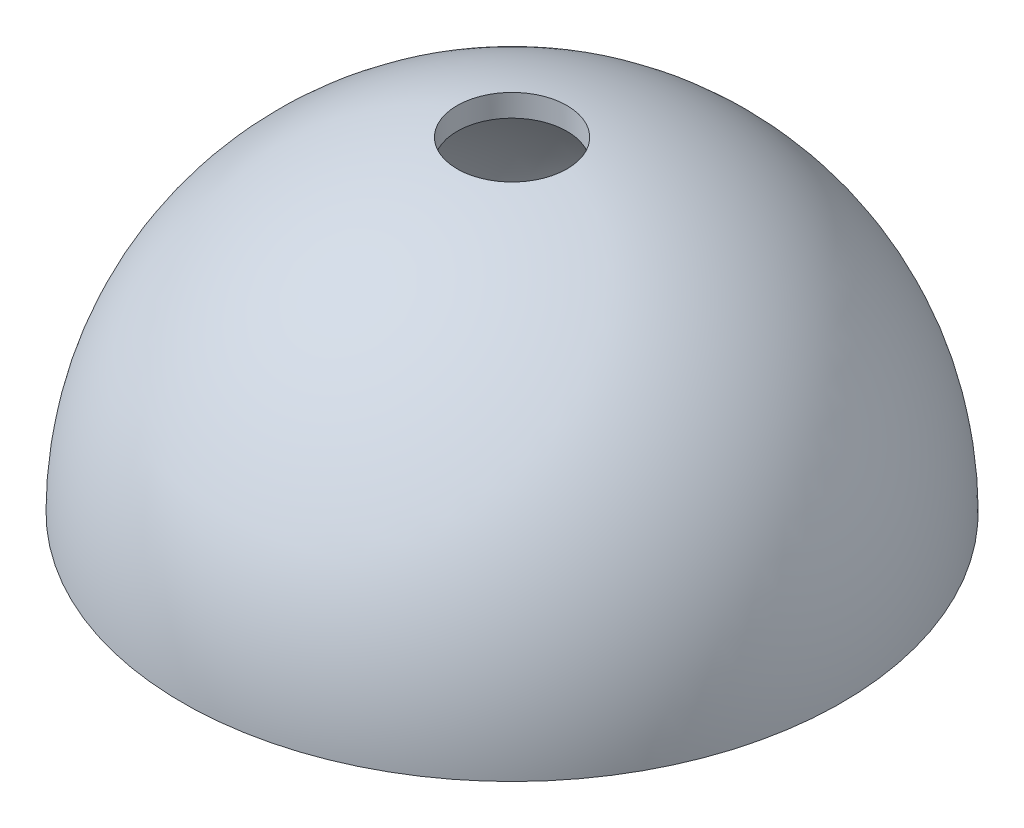
SolidWorks part; units mm, degrees
ref_plane "Front Plane" through (0, 0, 0) normal (0, 0, 1) x (1, 0, 0)
ref_plane "Top Plane" through (0, 0, 0) normal (0, 1, 0) x (1, 0, 0)
ref_plane "Right Plane" through (0, 0, 0) normal (1, 0, 0) x (0, 0, -1)
sketch "Sketch1" plane through (0, 0, 0) normal (0, 0, 1) x (1, 0, 0)
  line L0 (0, 0) -> (0, 150)
  line L1 (0, 0) -> (-150, 0)
  arc A0 (-150, 0) -> (0, 150) centre (0, 0) cw
  dimension "D1" = 150
revolve "Revolve1" add sketch "Sketch1" angle 360 about L0
shell "Shell1" thickness 10 removed face at (0, 0, -150)
sketch "Sketch2" plane through (0, 0, 0) normal (0, 1, 0) x (1, 0, 0)
  circle A0 centre (0, 0) radius 25
  dimension "D1" = 50
extrude "Cut-Extrude3" cut sketch "Sketch2" against normal through all and the other way through all
